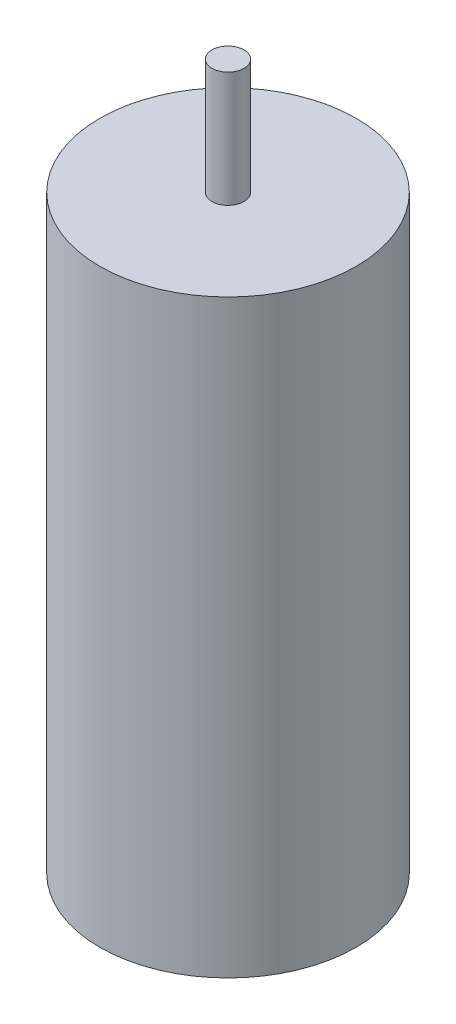
SolidWorks part; units mm, degrees
ref_plane "Front Plane" through (0, 0, 0) normal (0, 0, 1) x (1, 0, 0)
ref_plane "Top Plane" through (0, 0, 0) normal (0, 1, 0) x (1, 0, 0)
ref_plane "Right Plane" through (0, 0, 0) normal (1, 0, 0) x (0, 0, -1)
sketch "Sketch4" plane through (0, 0, 0) normal (0, 0, 1) x (1, 0, 0)
  line L0 (0, 88.1063) -> (0, -47.5917) construction
  line L1 (0, -40.3847) -> (20, -40.3847)
  line L2 (20, -40.3847) -> (20, 51.6153)
  line L3 (20, 51.6153) -> (2.5, 51.6153)
  line L4 (2.5, 51.6153) -> (2.5, 69.6153)
  line L5 (2.5, 69.6153) -> (0, 69.6153)
  line L6 (0, -40.3847) -> (0, 69.6153)
  dimension "D1" = 20
  dimension "D2" = 20
revolve "Revolve1" add sketch "Sketch4" angle 360 about L0
